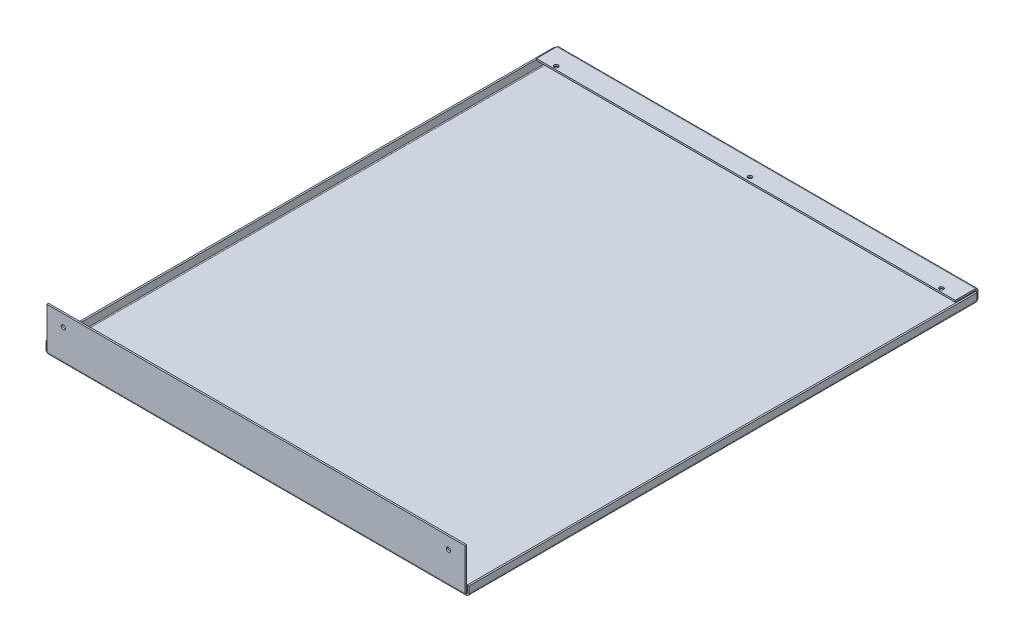
SolidWorks part; units mm, degrees
note: The reader was unsure of these and kept them because the rebuilt part matched: flange length of "Edge-Flange1", "Edge-Flange4", "Edge-Flange5", "Edge-Flange6", "Edge-Flange7".
material "Chrome Stainless Steel"
ref_plane "Front Plane" through (0, 0, 0) normal (0, 0, 1) x (1, 0, 0)
ref_plane "Top Plane" through (0, 0, 0) normal (0, 1, 0) x (1, 0, 0)
ref_plane "Right Plane" through (0, 0, 0) normal (1, 0, 0) x (0, 0, -1)
sketch "Sketch1" plane through (0, 0, 0) normal (0, 1, 0) x (1, 0, 0)
  line L1 (-249, 302) -> (249, 302)
  line L2 (-249, 302) -> (-249, -302)
  line L3 (-249, -302) -> (249, -302)
  line L4 (249, 302) -> (249, -302)
  line L5 (-249, 302) -> (249, -302) construction
  line L6 (-249, -302) -> (249, 302) construction
  point P0 (0, 0)
  dimension "D1" = 498
  dimension "D2" = 604
base flange "Base-Flange1" sketch "Sketch1" thickness 2 reverse thickness direction yes parameters "D1"=6.35
edge flange "Edge-Flange1" sketch "Sketch10" flange angle 90 flange length 10 flange position material outside bend radius 1 thickness 2 relief rectangular parameters "D6"=10
sketch "Sketch10" plane through (-249, 2, 0) normal (1, 0, 0) x (0, 0, -1)
  line L2 (-302, 0) -> (-302, 10)
  line L3 (-302, 10) -> (302, 10)
  line L4 (302, 10) -> (302, 0)
  line L5 (302, 0) -> (-302, 0) construction
  line L6 (302, 0) -> (-302, 0)
bend "EdgeBend1" bend radius 1 bend angle 90 parameters "D5"=1
edge flange "Edge-Flange4" sketch "Sketch19" flange angle 90 flange length 10 flange position material outside bend radius 1 thickness 2 relief none parameters "D6"=10
sketch "Sketch19" plane through (0, 2, -302) normal (0, 0, 1) x (1, 0, 0)
  line L2 (-248, 0) -> (-248, 10)
  line L3 (-248, 10) -> (249, 10)
  line L4 (249, 10) -> (249, 0)
  line L5 (249, 0) -> (-248, 0) construction
  line L6 (249, 0) -> (-248, 0)
bend "EdgeBend4" bend radius 1 bend angle 90 parameters "D5"=2
edge flange "Edge-Flange5" sketch "Sketch22" flange angle 90 flange length 25 flange position material outside bend radius 1 thickness 2 relief rectangular parameters "D6"=10
sketch "Sketch22" plane through (0, 12, -302) normal (0, -1, 0) x (1, 0, 0)
  line L2 (-248, 0) -> (-248, 25)
  line L3 (-248, 25) -> (249, 25)
  line L4 (249, 25) -> (249, 0)
  line L9 (249, 0) -> (-248, 0) construction
  line L10 (249, 0) -> (-248, 0)
bend "EdgeBend5" bend radius 1 bend angle 90 parameters "D5"=3
edge flange "Edge-Flange6" sketch "Sketch25" flange angle 90 flange length 9 flange position material outside bend radius 1 thickness 2 relief none parameters "D6"=10
sketch "Sketch25" plane through (249, 2, 0) normal (-1, 0, 0) x (0, 0, 1)
  line L2 (-301, 0) -> (-301, 9)
  line L3 (-301, 9) -> (302, 9)
  line L4 (302, 9) -> (302, 0)
  line L5 (302, 0) -> (-301, 0) construction
  line L6 (302, 0) -> (-301, 0)
bend "EdgeBend6" bend radius 1 bend angle 90 parameters "D5"=4
edge flange "Edge-Flange7" sketch "Sketch28" flange angle 90 flange length 50 flange position material outside bend radius 1 thickness 2 relief none parameters "D6"=10
sketch "Sketch28" plane through (0, 2, 302) normal (0, 0, -1) x (-1, 0, 0)
  line L2 (-248, 0) -> (-248, 50)
  line L3 (-248, 50) -> (248, 50)
  line L4 (248, 50) -> (248, 0)
  line L5 (248, 0) -> (-248, 0) construction
  line L6 (248, 0) -> (-248, 0)
bend "EdgeBend7" bend radius 1 bend angle 90 parameters "D5"=5
sketch "Sketch37" plane through (0, 14, 0) normal (0, 1, 0) x (1, 0, 0)
  line L0 (-248, 277) -> (-248, 301) construction
  line L1 (249, 277) -> (-248, 277) construction
  line L4 (249, 301) -> (249, 277) construction
  circle A0 centre (-228.5, 281) radius 2.5
  circle A1 centre (228.5, 281) radius 2.5
  point P4 (-248, 289)
  dimension "D3" = 5
  dimension "D4" = 5
  dimension "D1" = 19.5
  dimension "D2" = 4
  dimension "D5" = 4
  dimension "D6" = 20.5
extrude "Cut-Extrude2" cut sketch "Sketch37" against normal blind 2 normal cut yes
sketch "Sketch38" plane through (0, 0, 304) normal (0, 0, 1) x (1, 0, 0)
  line L0 (-248, 52) -> (248, 52) construction
  line L1 (248, 52) -> (248, 3) construction
  line L2 (0, 52) -> (0, 0) construction
  circle A0 centre (228.5, 38) radius 2.5
  circle A1 centre (-228.5, 38) radius 2.5
  dimension "D1" = 5
  dimension "D2" = 14
  dimension "D3" = 19.5
extrude "Cut-Extrude3" cut sketch "Sketch38" against normal through all normal cut yes
sketch "Sketch39" plane through (0, 14, 0) normal (0, 1, 0) x (1, 0, 0)
  line L7 (249, 277) -> (249, 301)
  line L8 (249, 301) -> (-248, 301)
  line L9 (-248, 301) -> (-248, 277)
  line L10 (-248, 277) -> (249, 277)
  line L11 (249, 277) -> (249, 301)
  line L12 (249, 301) -> (-248, 301)
  line L13 (-248, 301) -> (-248, 277)
  line L14 (-248, 277) -> (249, 277)
  circle A0 centre (0.4684, 282) radius 2.5
  dimension "D1" = 5
  dimension "D2" = 0
  dimension "D3" = 19
extrude "Cut-Extrude4" cut sketch "Sketch39" against normal blind 10 contours A0 normal cut yes
sketch "Bend-Lines1" [suppressed] plane through (0, 0, 0) normal (0, 1, 0) x (1, 0, 0)
sketch "Bounding-Box1" [suppressed] plane through (0, 0, 0) normal (0, 1, 0) x (1, 0, 0)
sheet metal parameters "Sheet-Metal1" thickness 2 parameters "D1"=6.35
flat pattern "Flat-Pattern1" [suppressed]
sketch "Bend-Lines2" plane through (0, 0, 0) normal (0, 1, 0) x (1, 0, 0)
sketch "Bounding-Box2" [suppressed] plane through (0, 0, 0) normal (0, 1, 0) x (1, 0, 0)
sheet metal parameters "Sheet-Metal2" thickness 2 parameters "D1"=6.35
flat pattern "Flat-Pattern1" [suppressed]
sketch "Bend-Lines2" plane through (0, 0, 0) normal (0, 1, 0) x (1, 0, 0)
sketch "Bounding-Box2" [suppressed] plane through (0, 0, 0) normal (0, 1, 0) x (1, 0, 0)
bend of the flat pattern "Flatten-<EdgeBend1>1"
sheet metal parameters "Sheet-Metal5" thickness 2 parameters "D1"=6.35
flat pattern "Flat-Pattern1" [suppressed]
sketch "Bend-Lines2" plane through (0, 0, 0) normal (0, 1, 0) x (1, 0, 0)
sketch "Bounding-Box2" [suppressed] plane through (0, 0, 0) normal (0, 1, 0) x (1, 0, 0)
bend of the flat pattern "Flatten-<EdgeBend1>1"
bend of the flat pattern "Flatten-<EdgeBend4>1"
sheet metal parameters "Sheet-Metal6" thickness 2 parameters "D1"=6.35
flat pattern "Flat-Pattern1" [suppressed]
sketch "Bend-Lines2" plane through (0, 0, 0) normal (0, 1, 0) x (1, 0, 0)
sketch "Bounding-Box2" [suppressed] plane through (0, 0, 0) normal (0, 1, 0) x (1, 0, 0)
bend of the flat pattern "Flatten-<EdgeBend1>1"
bend of the flat pattern "Flatten-<EdgeBend4>1"
bend of the flat pattern "Flatten-<EdgeBend5>1"
sheet metal parameters "Sheet-Metal7" thickness 2 parameters "D1"=6.35
flat pattern "Flat-Pattern1" [suppressed]
sketch "Bend-Lines2" plane through (0, 0, 0) normal (0, 1, 0) x (1, 0, 0)
sketch "Bounding-Box2" [suppressed] plane through (0, 0, 0) normal (0, 1, 0) x (1, 0, 0)
bend of the flat pattern "Flatten-<EdgeBend1>1"
bend of the flat pattern "Flatten-<EdgeBend4>1"
bend of the flat pattern "Flatten-<EdgeBend5>1"
bend of the flat pattern "Flatten-<EdgeBend6>1"
sheet metal parameters "Sheet-Metal8" thickness 2 parameters "D1"=6.35
flat pattern "Flat-Pattern1"
sketch "Bend-Lines2" plane through (0, 0, 0) normal (0, -1, 0) x (-1, 0, 0)
  line L0 (-249, -250.5708) -> (249, -250.5708) construction
  line L1 (-250.5708, 249) -> (-250.5708, -250) construction
  line L2 (249, 271.7124) -> (-250, 271.7124) construction
  line L3 (249, 250.5708) -> (-250, 250.5708) construction
  line L4 (250.5708, -250) -> (250.5708, 250) construction
  line L5 (-249, -250.5708) -> (249, -250.5708) construction
  line L6 (-250.5708, 249) -> (-250.5708, -250) construction
  line L7 (249, 271.7124) -> (-250, 271.7124) construction
  line L8 (249, 250.5708) -> (-250, 250.5708) construction
  line L9 (250.5708, -250) -> (250.5708, 250) construction
sketch3d "Bounding-Box2" [suppressed]
  line L0 (271.1416, 297.2832, 0) -> (271.1416, -301.1416, 0) construction
  line L1 (-270.1416, 297.2832, 0) -> (-270.1416, -301.1416, 0) construction
  line L2 (271.1416, 297.2832, 0) -> (-270.1416, 297.2832, 0) construction
  line L3 (271.1416, -301.1416, 0) -> (-270.1416, -301.1416, 0) construction
bend of the flat pattern "Flatten-<EdgeBend1>1"
bend of the flat pattern "Flatten-<EdgeBend4>1"
bend of the flat pattern "Flatten-<EdgeBend5>1"
bend of the flat pattern "Flatten-<EdgeBend6>1"
bend of the flat pattern "Flatten-<EdgeBend7>1"
sheet metal parameters "Sheet-Metal11" thickness 2 parameters "D1"=6.35
flat pattern "Flat-Pattern1"
sketch "Bend-Lines2" plane through (0, 0, 0) normal (0, -1, 0) x (-1, 0, 0)
  line L0 (-249, -250.5708) -> (249, -250.5708) construction
  line L1 (-250.5708, 249) -> (-250.5708, -250) construction
  line L2 (249, 271.7124) -> (-250, 271.7124) construction
  line L3 (249, 250.5708) -> (-250, 250.5708) construction
  line L4 (250.5708, -250) -> (250.5708, 250) construction
  line L5 (-249, -250.5708) -> (249, -250.5708) construction
  line L6 (-250.5708, 249) -> (-250.5708, -250) construction
  line L7 (249, 271.7124) -> (-250, 271.7124) construction
  line L8 (249, 250.5708) -> (-250, 250.5708) construction
  line L9 (250.5708, -250) -> (250.5708, 250) construction
sketch3d "Bounding-Box2" [suppressed]
  line L0 (271.1416, 297.2832, 0) -> (271.1416, -301.1416, 0) construction
  line L1 (-270.1416, 297.2832, 0) -> (-270.1416, -301.1416, 0) construction
  line L2 (271.1416, 297.2832, 0) -> (-270.1416, 297.2832, 0) construction
  line L3 (271.1416, -301.1416, 0) -> (-270.1416, -301.1416, 0) construction
bend of the flat pattern "Flatten-<EdgeBend1>1"
bend of the flat pattern "Flatten-<EdgeBend4>1"
bend of the flat pattern "Flatten-<EdgeBend5>1"
bend of the flat pattern "Flatten-<EdgeBend6>1"
bend of the flat pattern "Flatten-<EdgeBend7>1"
sheet metal parameters "Sheet-Metal12" thickness 2 parameters "D1"=6.35
flat pattern "Flat-Pattern1"
sketch "Bend-Lines2" plane through (0, 0, 0) normal (0, -1, 0) x (-1, 0, 0)
  line L0 (-249, -250.5708) -> (249, -250.5708) construction
  line L1 (-250.5708, 249) -> (-250.5708, -250) construction
  line L2 (249, 271.7124) -> (-250, 271.7124) construction
  line L3 (249, 250.5708) -> (-250, 250.5708) construction
  line L4 (250.5708, -250) -> (250.5708, 250) construction
  line L5 (-249, -250.5708) -> (249, -250.5708) construction
  line L6 (-250.5708, 249) -> (-250.5708, -250) construction
  line L7 (249, 271.7124) -> (-250, 271.7124) construction
  line L8 (249, 250.5708) -> (-250, 250.5708) construction
  line L9 (250.5708, -250) -> (250.5708, 250) construction
sketch3d "Bounding-Box2" [suppressed]
  line L0 (271.1416, 297.2832, 0) -> (271.1416, -301.1416, 0) construction
  line L1 (-270.1416, 297.2832, 0) -> (-270.1416, -301.1416, 0) construction
  line L2 (271.1416, 297.2832, 0) -> (-270.1416, 297.2832, 0) construction
  line L3 (271.1416, -301.1416, 0) -> (-270.1416, -301.1416, 0) construction
bend of the flat pattern "Flatten-<EdgeBend1>1"
bend of the flat pattern "Flatten-<EdgeBend4>1"
bend of the flat pattern "Flatten-<EdgeBend5>1"
bend of the flat pattern "Flatten-<EdgeBend6>1"
bend of the flat pattern "Flatten-<EdgeBend7>1"
sheet metal parameters "Sheet-Metal13" thickness 2 parameters "D1"=6.35
flat pattern "Flat-Pattern1"
sketch "Bend-Lines2" plane through (0, 0, 0) normal (0, -1, 0) x (-1, 0, 0)
  line L0 (-248, -302.5708) -> (248, -302.5708) construction
  line L1 (-249.5708, 301) -> (-249.5708, -302) construction
  line L2 (248, 313.7124) -> (-249, 313.7124) construction
  line L3 (248, 302.5708) -> (-249, 302.5708) construction
  line L4 (249.5708, -302) -> (249.5708, 302) construction
  line L5 (-248, -302.5708) -> (248, -302.5708) construction
  line L6 (-249.5708, 301) -> (-249.5708, -302) construction
  line L7 (248, 313.7124) -> (-249, 313.7124) construction
  line L8 (248, 302.5708) -> (-249, 302.5708) construction
  line L9 (249.5708, -302) -> (249.5708, 302) construction
sketch3d "Bounding-Box2" [suppressed]
  line L0 (260.1416, 339.2832, 0) -> (260.1416, -353.1416, 0) construction
  line L1 (-259.1416, 339.2832, 0) -> (-259.1416, -353.1416, 0) construction
  line L2 (260.1416, 339.2832, 0) -> (-259.1416, 339.2832, 0) construction
  line L3 (260.1416, -353.1416, 0) -> (-259.1416, -353.1416, 0) construction
bend of the flat pattern "Flatten-<EdgeBend1>1"
bend of the flat pattern "Flatten-<EdgeBend4>1"
bend of the flat pattern "Flatten-<EdgeBend5>1"
bend of the flat pattern "Flatten-<EdgeBend6>1"
bend of the flat pattern "Flatten-<EdgeBend7>1"
